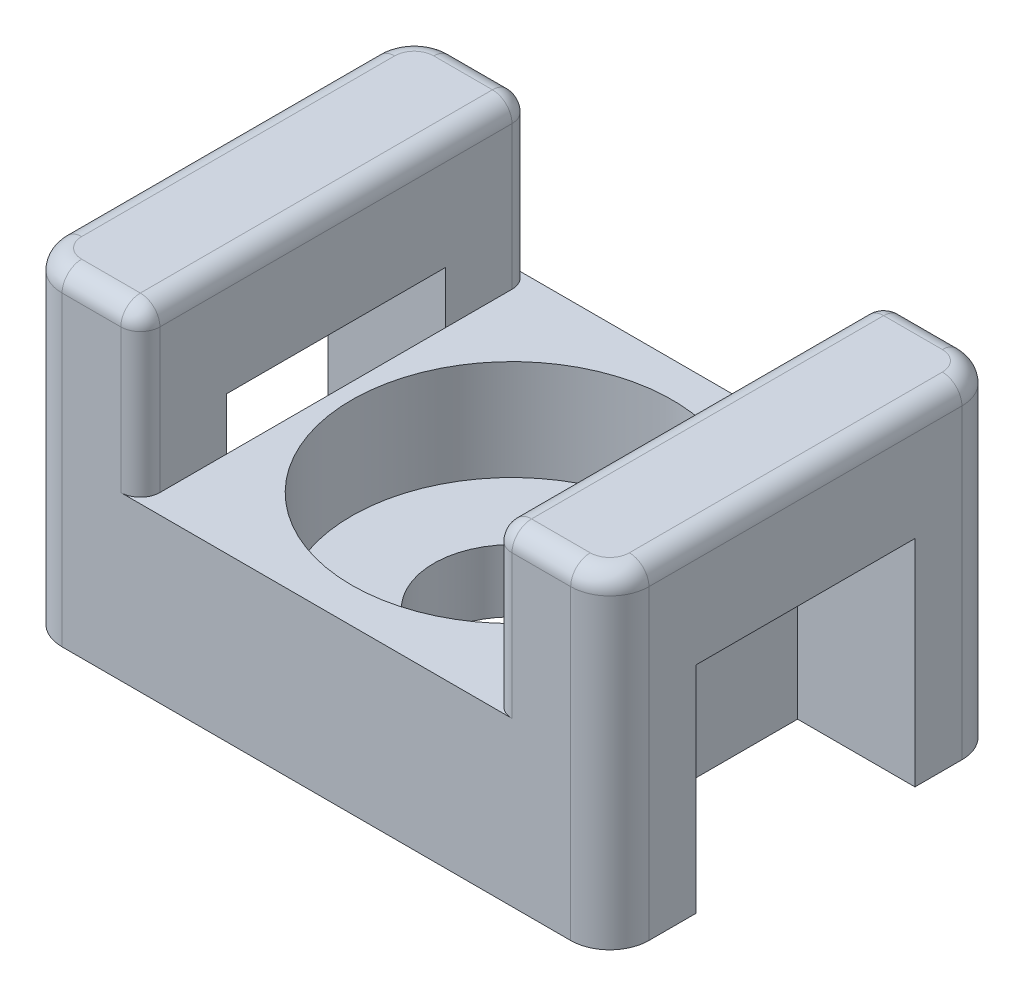
SolidWorks part; units mm, degrees
ref_plane "Front Plane" through (0, 0, 0) normal (0, 0, 1) x (1, 0, 0)
ref_plane "Top Plane" through (0, 0, 0) normal (0, 1, 0) x (1, 0, 0)
ref_plane "Right Plane" through (0, 0, 0) normal (1, 0, 0) x (0, 0, -1)
sketch "Sketch1" plane through (0, 0, 0) normal (0, 1, 0) x (1, 0, 0)
  line L1 (7.1438, -4.7625) -> (-7.1437, -4.7625)
  line L2 (7.1438, -4.7625) -> (7.1438, 4.7625)
  line L3 (7.1438, 4.7625) -> (-7.1437, 4.7625)
  line L4 (-7.1437, -4.7625) -> (-7.1437, 4.7625)
  line L5 (7.1438, -4.7625) -> (-7.1437, 4.7625) construction
  line L6 (7.1438, 4.7625) -> (-7.1437, -4.7625) construction
  circle A0 centre (0, 0) radius 1.905
  dimension "MT" = 3.81
  dimension "Length" = 14.2875
  dimension "Width" = 9.525
extrude "Boss-Extrude1" add sketch "Sketch1" along normal blind 7.9375
sketch "Sketch2" plane through (0, 0, 4.7625) normal (0, 0, 1) x (1, 0, 0)
  line L0 (-4.2862, 7.9375) -> (-4.2862, 3.9688)
  line L1 (-7.1437, 7.9375) -> (7.1438, 7.9375) construction
  line L2 (-4.2862, 3.9688) -> (4.2862, 3.9688)
  line L3 (4.2862, 3.9688) -> (4.2862, 7.9375)
  line L4 (0, 0) -> (0, 3.9688) construction
  line L5 (-7.1437, 0) -> (7.1438, 0) construction
  line L6 (4.2862, 3.9688) -> (7.1437, 3.9688) construction
  line L7 (7.1438, 7.9375) -> (7.1438, 0) construction
  line L8 (-4.2862, 7.9375) -> (4.2862, 7.9375)
  line L9 (-7.1437, 7.9375) -> (-7.1437, 0) construction
  dimension "D1" = 8.5725
  dimension "D2" = 2.8575
extrude "Cut-Extrude1" cut sketch "Sketch2" against normal through all
sketch "Sketch3" plane through (0, 0, 0) normal (1, 0, 0) x (0, 0, -1)
  line L0 (0, 0) -> (0, 3.9688) construction
  line L1 (-2.667, 5.2388) -> (2.667, 5.2388)
  line L2 (-2.667, 5.2388) -> (-2.667, 3.9688)
  line L3 (-2.667, 3.9688) -> (2.667, 3.9688)
  line L4 (2.667, 5.2388) -> (2.667, 3.9688)
  line L5 (-4.7625, 0) -> (4.7625, 0) construction
  line L6 (4.7625, 3.9688) -> (-4.7625, 3.9688) construction
  dimension "CH" = 1.27
  dimension "CW" = 5.334
extrude "Cut-Extrude2" cut sketch "Sketch3" against normal through all both and the other way through all
sketch "Sketch4" plane through (7.1438, 0, 0) normal (1, 0, 0) x (0, 0, -1)
  line L0 (-4.7625, 0) -> (4.7625, 0) construction
  line L1 (-2.667, 3.9688) -> (2.667, 3.9688)
  line L2 (-2.667, 3.9688) -> (-2.667, 0)
  line L3 (-2.667, 0) -> (2.667, 0)
  line L4 (2.667, 3.9688) -> (2.667, 0)
  line L5 (2.667, 3.9688) -> (2.667, 5.2388) construction
extrude "Cut-Extrude3" cut sketch "Sketch4" against normal up to vertex (2.8575 mm away) up to point (4.2862, 7.9375, -4.7625)
sketch "Sketch5" plane through (-7.1437, 0, 0) normal (-1, 0, 0) x (0, 0, 1)
  line L4 (2.667, 3.9688) -> (-2.667, 3.9688)
  line L5 (-2.667, 3.9688) -> (-2.667, 0)
  line L6 (-2.667, 0) -> (2.667, 0)
  line L7 (2.667, 0) -> (2.667, 3.9688)
  line L8 (2.667, 3.9688) -> (-2.667, 3.9688)
  line L9 (-2.667, 3.9688) -> (-2.667, 0)
  line L10 (-2.667, 0) -> (2.667, 0)
  line L11 (2.667, 0) -> (2.667, 3.9688)
  dimension "D1" = 0
extrude "Cut-Extrude4" cut sketch "Sketch5" against normal up to vertex (2.8575 mm away) up to point (-4.2862, 7.9375, -4.7625)
sketch "Sketch6" plane through (0, 3.9688, 0) normal (0, 1, 0) x (1, 0, 0)
  line L10 (3.9053, 2.667) -> (3.9053, -2.667)
  line L11 (3.9053, 2.667) -> (3.9053, -2.667) construction
  circle A0 centre (0, 0) radius 3.9053
  dimension "D1" = 0.381
extrude "Cut-Extrude5" cut sketch "Sketch6" against normal offset from surface (2.4448 mm away) 1.524 up to face at (0, 0, 0)
fillet "Fillet2" radius 0.9525 4 edges at (-7.1437, 3.9688, -4.7625) (-7.1437, 3.9688, 4.7625) (7.1438, 3.9688, -4.7625) (7.1438, 3.9688, 4.7625)
fillet "Fillet3" radius 0.4762 16 edges at (-4.2862, 7.9375, 0) (-5.2387, 7.9375, 4.7625) (-6.8648, 7.9375, 4.4835) (-7.1437, 7.9375, 0) (-6.8648, 7.9375, -4.4835) (-5.2387, 7.9375, -4.7625) (6.8648, 7.9375, 4.4835) (5.2388, 7.9375, 4.7625) (4.2862, 7.9375, 0) (5.2388, 7.9375, -4.7625) (6.8648, 7.9375, -4.4835) (7.1438, 7.9375, 0) (4.2862, 5.9531, -4.7625) (4.2862, 5.9531, 4.7625) (-4.2862, 5.9531, -4.7625) (-4.2862, 5.9531, 4.7625)
scale "Scale1" scale about centroid uniform scaling yes scale factor 1.323529
equation "\"D1@Sketch2\"=\"Length@Sketch1\"*.6"
equation "\"D1@Fillet2\"=\"D2@Sketch2\"/3"
equation "\"D1@Fillet3\"=\"D1@Fillet2\"/2"
